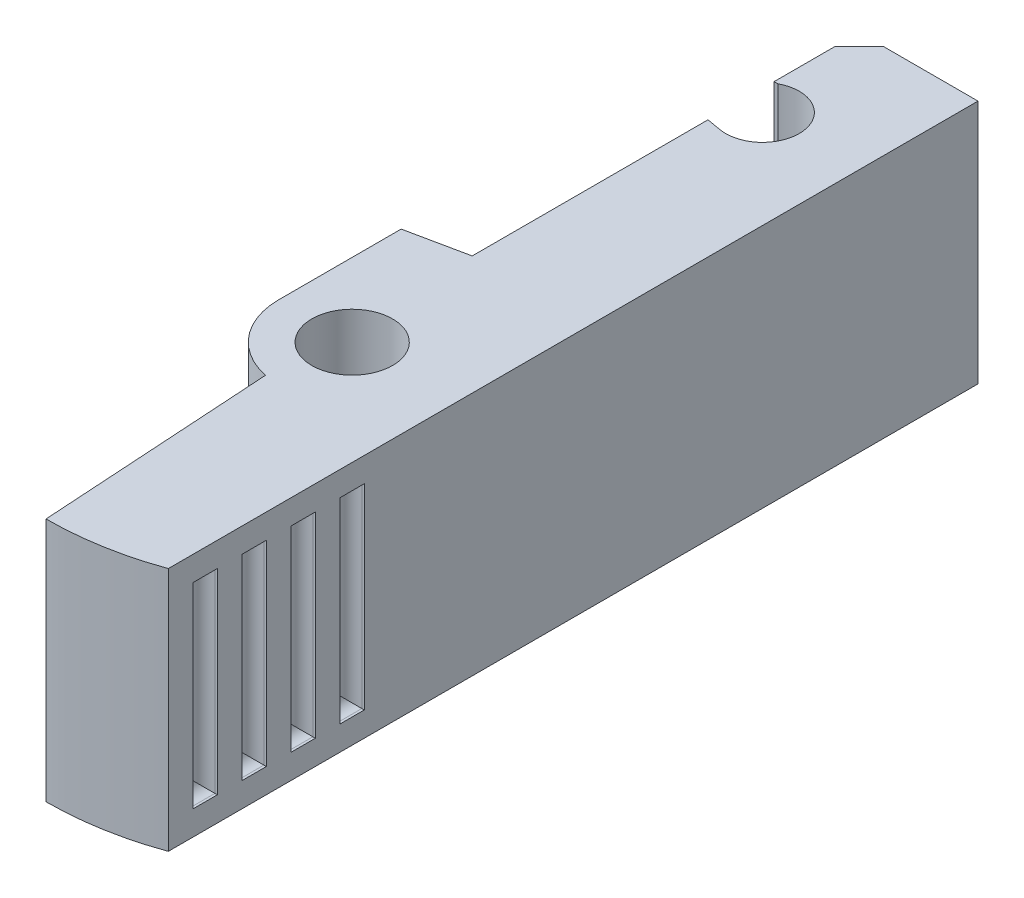
SolidWorks part; units mm, degrees
ref_plane "Front Plane" through (0, 0, 0) normal (0, 0, 1) x (1, 0, 0)
ref_plane "Top Plane" through (0, 0, 0) normal (0, 1, 0) x (1, 0, 0)
ref_plane "Right Plane" through (0, 0, 0) normal (1, 0, 0) x (0, 0, -1)
sketch "Sketch1" plane through (0, 0, 0) normal (0, 1, 0) x (1, 0, 0)
  line L0 (0, -18.6887) -> (0, 17.743) construction
  line L1 (-8.8335, 16.5) -> (8.9277, 16.5) construction
  line L2 (-9.6992, 0) -> (9.6992, 0) construction
  line L3 (-9.7784, -12.5) -> (9.7784, -12.5) construction
  line L4 (4.25, 21.3) -> (4.25, -17.7645) construction
  line L7 (4.25, 21.3) -> (4.25, -11.7553)
  line L9 (0, -12.5) -> (-0.6, -2.9394)
  line L10 (-3, 18.2158) -> (-3, -18.2158) construction
  line L11 (-0.6, 20.3) -> (-0.6, -18.2158) construction
  line L12 (-0.6, 15.1268) -> (-0.6, 5.5)
  line L13 (-0.6, 5.5) -> (-3, 5)
  line L14 (-3, 5) -> (-3, 0)
  line L15 (-0.6, 17.8266) -> (-0.6, 20.3)
  line L16 (-0.6, 20.3) -> (0.4, 21.3)
  line L17 (0.4, 21.3) -> (4.25, 21.3)
  line L19 (0.25, 21.3) -> (0.25, 13.2183) construction
  line L20 (-0.6, 15.1268) -> (0, 15.021)
  line L21 (-0.6, 17.8266) -> (-0.45, 17.8266)
  circle A0 centre (0, 0) radius 1.65
  arc A2 (-0.6, -2.9394) -> (-3, 0) centre (0, 0) cw
  arc A3 (0, -12.5) -> (4.25, -11.7553) centre (0, 0) ccw
  arc A5 (0, 15.021) -> (-0.45, 17.8266) centre (0.25, 16.5) ccw
  point P10 (0, -12.5)
  point P22 (0, 15.021)
  point P26 (0, 0)
  point P29 (0, 0)
  point P31 (0, 0)
  point P35 (0, 0)
  point P36 (0.25, 13.2183)
  point P37 (0, 0)
  point P38 (-0.6, 20.2091)
  point P39 (0, 0)
  point P42 (4.25, 25.1149)
  point P43 (4.25, 21.0747)
  dimension "D3" = 3.3
  dimension "D5" = 5
  dimension "D8" = 80
  dimension "D15" = 1.5
  dimension "D1" = 16.5
  dimension "D2" = 12.5
  dimension "D4" = 4.25
  dimension "D6" = 3
  dimension "D7" = 0.6
  dimension "D9" = 135
  dimension "D10" = 11
  dimension "D11" = 0.25
  dimension "D12" = 4.8
  dimension "D13" = 135
  dimension "D14" = 0.4
  dimension "D16" = 0.15
  dimension "D17" = 9.6268
  dimension "D18" = 2.4734
extrude "Boss-Extrude1" add sketch "Sketch1" along normal blind 10
sketch "Sketch2" plane through (4.25, 0, 0) normal (1, 0, 0) x (0, 0, -1)
  line L0 (-16.2424, 5) -> (17.4778, 5) construction
  line L1 (20.3, 0) -> (-18.2158, 0) construction
  line L2 (0, 0) -> (0, 10) construction
  line L3 (-11.7553, 10) -> (21.3, 10) construction
  line L4 (-7, 10) -> (-7, 0) construction
  line L5 (21.3, 0) -> (-11.7553, 0) construction
  circle A0 centre (-7, 5) radius 2.5
  dimension "D3" = 5
  dimension "D1" = 5
  dimension "D2" = 7
extrude "Cut-Extrude1" cut sketch "Sketch2" against normal blind 10 from offset 2 offset against normal yes
sketch "Sketch3" plane through (4.25, 0, 0) normal (1, 0, 0) x (0, 0, -1)
  line L0 (-11.7553, 10) -> (-11.7553, 0) construction
  line L1 (-10.7553, 9) -> (-9.7553, 9)
  line L2 (-10.7553, 9) -> (-10.7553, 1)
  line L3 (-10.7553, 1) -> (-9.7553, 1)
  line L4 (-9.7553, 9) -> (-9.7553, 1)
  line L5 (-8.7553, 9) -> (-7.7553, 9)
  line L6 (-8.7553, 9) -> (-8.7553, 1)
  line L7 (-8.7553, 1) -> (-7.7553, 1)
  line L8 (-7.7553, 9) -> (-7.7553, 1)
  line L9 (-6.7553, 9) -> (-5.7553, 9)
  line L10 (-6.7553, 9) -> (-6.7553, 1)
  line L11 (-6.7553, 1) -> (-5.7553, 1)
  line L12 (-5.7553, 9) -> (-5.7553, 1)
  line L13 (-11.7553, 10) -> (21.3, 10) construction
  line L14 (18.2158, 0) -> (-18.2158, 0) construction
  line L16 (-4.7553, 9) -> (-3.7553, 9)
  line L17 (-4.7553, 9) -> (-4.7553, 1)
  line L18 (-4.7553, 1) -> (-3.7553, 1)
  line L19 (-3.7553, 9) -> (-3.7553, 1)
  point P14 (-10.2553, 9)
  dimension "D1" = 1
  dimension "D2" = 1
  dimension "D3" = 1
  dimension "D4" = 1
  dimension "D5" = 1
  dimension "D6" = 1
  dimension "D7" = 1
  dimension "D8" = 1
  dimension "D9" = 1
  dimension "D10" = 1
  dimension "D11" = 1
  dimension "D12" = 1
  dimension "D13" = 1
  dimension "D14" = 1
  dimension "D15" = 1
  dimension "D16" = 1
extrude "Cut-Extrude2" cut sketch "Sketch3" against normal blind 0.6
fillet "Fillet1" radius 0.5 16 edges at (3.65, 9, 4.2553) (3.65, 5, 3.7553) (3.65, 1, 4.2553) (3.65, 5, 4.7553) (3.65, 9, 6.2553) (3.65, 5, 5.7553) (3.65, 1, 6.2553) (3.65, 5, 6.7553) (3.65, 9, 8.2553) (3.65, 5, 7.7553) (3.65, 1, 8.2553) (3.65, 5, 8.7553) (3.65, 9, 10.2553) (3.65, 5, 9.7553) (3.65, 1, 10.2553) (3.65, 5, 10.7553)
